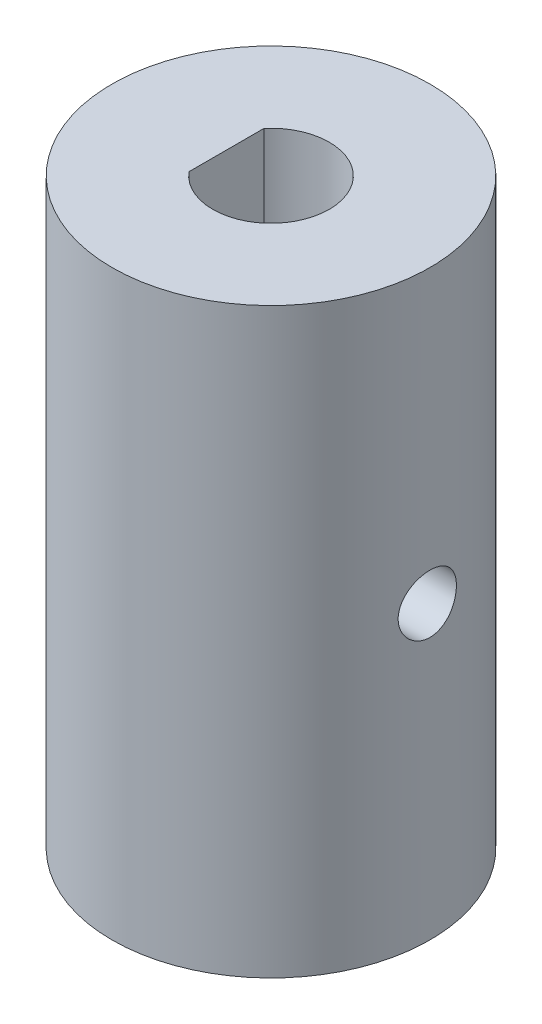
SolidWorks part; units mm, degrees
ref_plane "Front Plane" through (0, 0, 0) normal (0, 0, 1) x (1, 0, 0)
ref_plane "Top Plane" through (0, 0, 0) normal (0, 1, 0) x (1, 0, 0)
ref_plane "Right Plane" through (0, 0, 0) normal (1, 0, 0) x (0, 0, -1)
sketch "Sketch1" plane through (0, 0, 0) normal (0, 1, 0) x (1, 0, 0)
  circle A0 centre (0, 0) radius 8.189
extrude "Boss-Extrude1" add sketch "Sketch1" along normal blind 30
sketch "Sketch2" plane through (0, 30, 0) normal (0, 1, 0) x (1, 0, 0)
  circle A0 centre (0, 0) radius 3
extrude "Cut-Extrude1" cut sketch "Sketch2" against normal blind 30
sketch "Sketch4" plane through (0, 30, 0) normal (0, 1, 0) x (1, 0, 0)
  line L1 (-2.2951, -1.932) -> (-4.1343, -1.932)
  line L2 (-2.2951, -1.932) -> (-2.2951, 2.2587)
  line L3 (-2.2951, 2.2587) -> (-4.1343, 2.2587)
  line L4 (-4.1343, -1.932) -> (-4.1343, 2.2587)
  circle A0 centre (0, 0) radius 3 construction
extrude "Boss-Extrude2" add sketch "Sketch4" against normal blind 10
sketch "Sketch3" plane through (0, 0, 0) normal (1, 0, 0) x (0, 0, -1)
  circle A0 centre (0, 15) radius 1.5
extrude "Cut-Extrude2" cut sketch "Sketch3" against normal blind 10 and the other way blind 10
